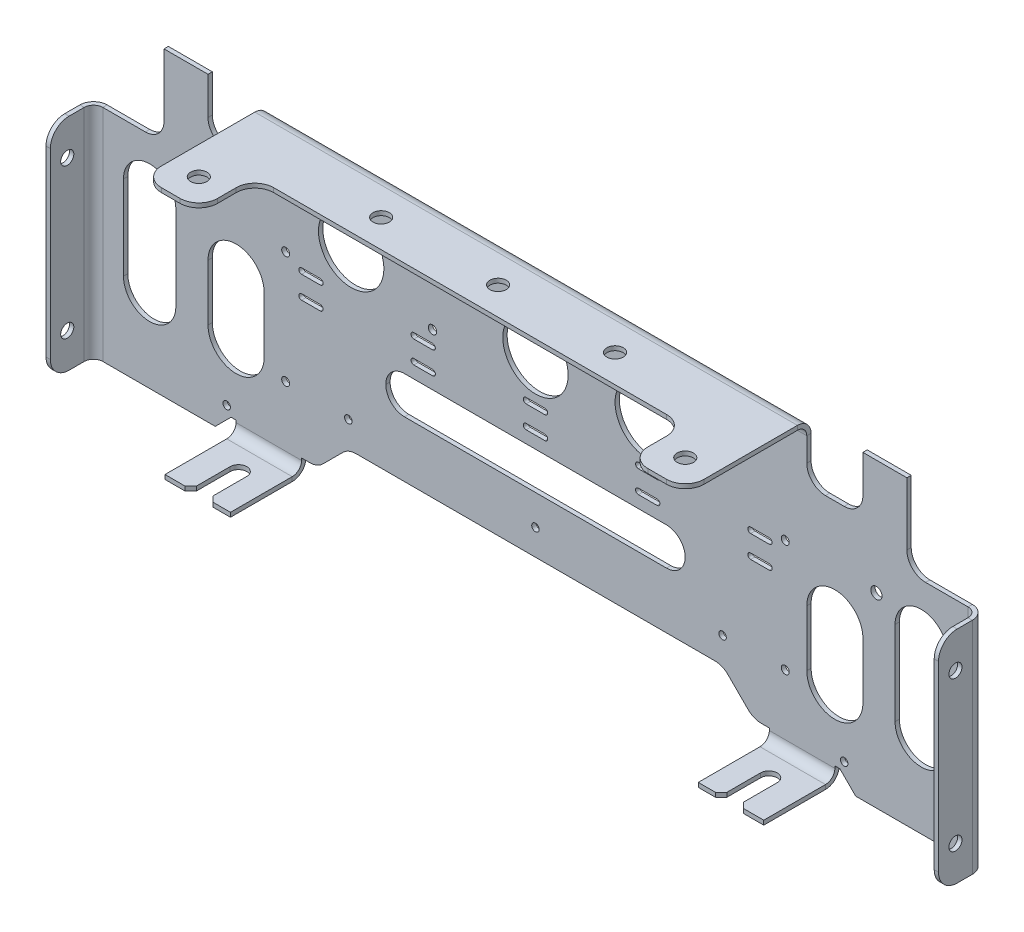
SolidWorks part; units mm, degrees
note: The reader was unsure of these and kept them because the rebuilt part matched: thickness of "Base-Flange1", "Edge-Flange1", "Edge-Flange2", "Edge-Flange3", "Sheet-Metal1", "Sheet-Metal2", "Sheet-Metal3", "Sheet-Metal4", "Sheet-Metal5", "Sheet-Metal6", "Sheet-Metal7", "Sheet-Metal14", "Sheet-Metal20", "Sheet-Metal21", "Sheet-Metal22", "Sheet-Metal24", "Sheet-Metal27", "Sheet-Metal28", "Sheet-Metal29", "Sheet-Metal30", "Sheet-Metal31", "Sheet-Metal32", "Sheet-Metal33"; flange length of "Edge-Flange1", "Edge-Flange2", "Edge-Flange3".
material "5052-H32"
ref_plane "Front Plane" through (0, 0, 0) normal (0, 0, 1) x (1, 0, 0)
ref_plane "Top Plane" through (0, 0, 0) normal (0, 1, 0) x (1, 0, 0)
ref_plane "Right Plane" through (0, 0, 0) normal (1, 0, 0) x (0, 0, -1)
sketch "Sketch1" plane through (0, 0, 0) normal (0, 0, 1) x (1, 0, 0)
  line L1 (238.5, 63.81) -> (-238.5, 63.81)
  line L2 (238.5, 63.81) -> (238.5, -63.81)
  line L3 (238.5, -63.81) -> (-238.5, -63.81)
  line L4 (-238.5, 63.81) -> (-238.5, -63.81)
  line L5 (238.5, 63.81) -> (-238.5, -63.81) construction
  line L6 (238.5, -63.81) -> (-238.5, 63.81) construction
  point P0 (0, 0)
  dimension "D1" = 477
  dimension "D2" = 127.62
base flange "Base-Flange1" sketch "Sketch1" thickness 2.31 reverse thickness direction no parameters "D1"=5
edge flange "Edge-Flange1" sketch "Sketch10" flange profiles "Sketch10", "Sketch11" flange angle 90 flange length 25.4 flange position material inside bend radius 5 thickness 2.31 parameters "D6"=10, "D8"=5.08
sketch "Sketch10" plane through (-238.5, 0, 0) normal (-1, 0, 0) x (0, -1, 0)
  line L2 (-63.81, 0) -> (-63.81, 23.09)
  line L3 (-63.81, 23.09) -> (63.81, 23.09)
  line L4 (63.81, 23.09) -> (63.81, 0)
  line L5 (-63.81, 0) -> (63.81, 0) construction
  line L6 (-63.81, 0) -> (63.81, 0)
sketch "Sketch11" plane through (238.5, 0, 0) normal (1, 0, 0) x (0, 1, 0)
  line L0 (-63.81, 0) -> (63.81, 0) construction
  line L1 (-63.81, 0) -> (63.81, 0)
  line L2 (-63.81, 0) -> (-63.81, 23.09)
  line L3 (-63.81, 23.09) -> (63.81, 23.09)
  line L4 (63.81, 23.09) -> (63.81, 0)
bend "EdgeBend1" bend radius 5 bend angle 90 parameters "D5"=1
bend "EdgeBend2" bend radius 5 bend angle 90 parameters "D5"=2
sketch "Sketch12" plane through (0, 0, 23.09) normal (0, 0, 1) x (1, 0, 0)
  line L0 (0, 63.81) -> (0, -63.81) construction
  line L1 (-238.5, 63.81) -> (-198.5, 63.81)
  line L2 (-238.5, 63.81) -> (-238.5, 53.81)
  line L3 (-238.5, 53.81) -> (-198.5, 53.81)
  line L4 (-198.5, 63.81) -> (-198.5, 53.81)
  line L5 (231.19, 63.81) -> (-231.19, 63.81) construction
  line L6 (-231.19, -63.81) -> (231.19, -63.81) construction
  line L7 (198.5, 63.81) -> (198.5, 53.81)
  line L8 (238.5, 53.81) -> (198.5, 53.81)
  line L9 (238.5, 63.81) -> (238.5, 53.81)
  line L10 (238.5, 63.81) -> (198.5, 63.81)
  dimension "D1" = 10
  dimension "D2" = 40
extrude "Cut-Extrude1" cut sketch "Sketch12" against normal through all
sketch "Sketch14" plane through (0, 0, 0) normal (0, 0, 1) x (1, 0, 0)
  line L0 (-231.19, -63.81) -> (231.19, -63.81) construction
  line L1 (198.5, 63.81) -> (-198.5, 63.81)
  line L2 (198.5, 63.81) -> (198.5, 97.24)
  line L3 (198.5, 97.24) -> (-198.5, 97.24)
  line L4 (-198.5, 63.81) -> (-198.5, 97.24)
  dimension "D1" = 161.05
extrude "Boss-Extrude1" add sketch "Sketch14" against normal up to surface (2.31 mm away) up to face at (0, 26.905, -2.31)
fillet "Fillet1" radius 10 4 edges at (-198.5, 53.81, -1.155) (198.5, 53.81, -1.155) (-237.345, 53.81, 23.09) (237.345, 53.81, 23.09)
sketch "Sketch15" plane through (238.5, 0, 0) normal (1, 0, 0) x (0, 0, -1)
  line L0 (-14.045, 35) -> (-14.045, -45) construction
  line L1 (-23.09, 43.81) -> (-23.09, -63.81) construction
  line L2 (-5, 53.81) -> (-5, -63.81) construction
  circle A0 centre (-14.045, 35) radius 3.5
  circle A1 centre (-14.045, -45) radius 3.5
  point P4 (-5, -5)
  point P6 (-14.045, -5)
  dimension "D1" = 7
  dimension "D2" = 80
  dimension "D3" = 9.045
extrude "Cut-Extrude3" cut sketch "Sketch15" against normal through all
sketch "Sketch16" plane through (0, 0, 0) normal (0, 0, 1) x (1, 0, 0)
  line L0 (125, -63.81) -> (100, -38.81)
  line L1 (-231.19, -63.81) -> (231.19, -63.81) construction
  line L2 (100, -38.81) -> (-100, -38.81)
  line L3 (-100, -38.81) -> (-125, -63.81)
  line L4 (-125, -63.81) -> (125, -63.81)
  point P4 (0, -63.81)
  dimension "D1" = 45
  dimension "D2" = 250
  dimension "D3" = 25
extrude "Cut-Extrude4" cut sketch "Sketch16" against normal blind 10
sketch "Sketch17" plane through (0, 0, 0) normal (0, 0, 1) x (1, 0, 0)
  line L0 (-160, 11.19) -> (-160, -18.81) construction
  line L1 (-145, 11.19) -> (-145, -18.81)
  line L2 (-175, 11.19) -> (-175, -18.81)
  line L3 (0, -38.81) -> (0, 97.24) construction
  line L4 (-100, -38.81) -> (100, -38.81) construction
  line L5 (198.5, 97.24) -> (-198.5, 97.24) construction
  line L6 (-231.19, -63.81) -> (-125, -63.81) construction
  line L7 (160, 11.19) -> (160, -18.81) construction
  line L8 (145, 11.19) -> (145, -18.81)
  line L9 (175, 11.19) -> (175, -18.81)
  line L10 (-206.19, 26.19) -> (-206.19, -18.81) construction
  line L11 (-192.19, 26.19) -> (-192.19, -18.81)
  line L12 (-220.19, 26.19) -> (-220.19, -18.81)
  line L13 (-231.19, -63.81) -> (-231.19, 53.81) construction
  line L14 (206.19, 26.19) -> (206.19, -18.81) construction
  line L15 (192.19, 26.19) -> (192.19, -18.81)
  line L16 (220.19, 26.19) -> (220.19, -18.81)
  line L17 (198.5, 97.24) -> (-198.5, 97.24) construction
  line L18 (175, 97.24) -> (145, 97.24)
  line L19 (175, 97.24) -> (175, 67.24)
  line L20 (175, 67.24) -> (145, 67.24)
  line L21 (145, 97.24) -> (145, 67.24)
  line L22 (-145, 97.24) -> (-145, 67.24)
  line L23 (-175, 67.24) -> (-145, 67.24)
  line L24 (-175, 97.24) -> (-175, 67.24)
  line L25 (-175, 97.24) -> (-145, 97.24)
  arc A0 (-145, 11.19) -> (-175, 11.19) centre (-160, 11.19) ccw
  arc A1 (-175, -18.81) -> (-145, -18.81) centre (-160, -18.81) ccw
  arc A2 (145, 11.19) -> (175, 11.19) centre (160, 11.19) cw
  arc A3 (175, -18.81) -> (145, -18.81) centre (160, -18.81) cw
  arc A4 (-192.19, 26.19) -> (-220.19, 26.19) centre (-206.19, 26.19) ccw
  arc A5 (-220.19, -18.81) -> (-192.19, -18.81) centre (-206.19, -18.81) ccw
  arc A6 (192.19, 26.19) -> (220.19, 26.19) centre (206.19, 26.19) cw
  arc A7 (220.19, -18.81) -> (192.19, -18.81) centre (206.19, -18.81) cw
  point P2 (-160, -3.81)
  point P18 (160, -3.81)
  point P25 (-206.19, 3.69)
  point P34 (206.19, 3.69)
  dimension "D2" = 15
  dimension "D5" = 14
  dimension "D1" = 30
  dimension "D3" = 60
  dimension "D4" = 160
  dimension "D6" = 25
  dimension "D7" = 45
  dimension "D8" = 30
extrude "Cut-Extrude5" cut sketch "Sketch17" against normal blind 10
sketch "Sketch18" plane through (0, 0, -2.31) normal (0, 0, -1) x (-1, 0, 0)
  line L0 (100, -38.81) -> (-100, -38.81) construction
  line L1 (80, 11.19) -> (-80, 11.19)
  line L2 (80, 11.19) -> (80, -8.81)
  line L3 (80, -8.81) -> (-80, -8.81)
  line L4 (-80, 11.19) -> (-80, -8.81)
  line L5 (80, 11.19) -> (-80, -8.81) construction
  line L6 (80, -8.81) -> (-80, 11.19) construction
  point P0 (0, 1.19)
  dimension "D1" = 20
  dimension "D2" = 160
  dimension "D3" = 30
extrude "Cut-Extrude6" cut sketch "Sketch18" against normal blind 10
sketch "Sketch19" plane through (0, 0, -2.31) normal (0, 0, -1) x (-1, 0, 0)
  line L0 (165, -50.955) -> (-165, -50.955) construction
  line L1 (-165, -50.955) -> (-100, -25) construction
  line L2 (-100, -25) -> (0, -25) construction
  line L3 (0, -25) -> (100, -25) construction
  line L4 (100, -25) -> (165, -50.955) construction
  circle A0 centre (0, -25) radius 2
  circle A1 centre (100, -25) radius 2
  circle A2 centre (165, -50.955) radius 2
  circle A3 centre (-100, -25) radius 2
  circle A4 centre (-165, -50.955) radius 2
  dimension "D1" = 4
  dimension "D2" = 330
  dimension "D3" = 25.955
  dimension "D4" = 65
  dimension "D5" = 25
extrude "Cut-Extrude8" cut sketch "Sketch19" against normal up to surface (2.31 mm away)
sketch "Sketch20" plane through (0, 0, -2.31) normal (0, 0, -1) x (-1, 0, 0)
  line L0 (60, 54.215) -> (-60, 54.215) construction
  line L1 (0, 11.19) -> (0, 97.24) construction
  line L2 (198.5, 63.81) -> (198.5, 97.24) construction
  line L3 (80, 11.19) -> (-80, 11.19) construction
  line L4 (-145, 97.24) -> (145, 97.24) construction
  circle A0 centre (0, 54.215) radius 17.4625
  circle A1 centre (98.5, 54.215) radius 17.4625
  circle A2 centre (-60, 54.215) radius 17.4625
  dimension "D1" = 34.925
  dimension "D2" = 120
  dimension "D3" = 100
extrude "Cut-Extrude9" cut sketch "Sketch20" against normal blind 10
fillet "Fillet2" radius 10 12 edges at (-80, -8.81, -1.155) (80, -8.81, -1.155) (80, 11.19, -1.155) (-80, 11.19, -1.155) (-100, -38.81, -1.155) (100, -38.81, -1.155) (-175, 67.24, -1.155) (-145, 67.24, -1.155) (175, 67.24, -1.155) (145, 67.24, -1.155) (237.345, -63.81, 23.09) (-237.345, -63.81, 23.09)
edge flange "Edge-Flange2" sketch "Sketch28" flange angle 90 flange length 34.925 flange position material inside bend radius 5 thickness 2.31 parameters "D1"=9.525, "D6"=10
bend "EdgeBend4" bend radius 5 bend angle 90 parameters "D5"=3
sketch "Sketch28" plane through (0, 97.24, 0) normal (0, 1, 0) x (-1, 0, 0)
  line L1 (-145, 0) -> (145, 0) construction
  line L2 (145, 0) -> (145, 34.925)
  line L3 (145, 34.925) -> (-145, 34.925)
  line L4 (-145, 34.925) -> (-145, 0)
  line L5 (-145, 0) -> (145, 0)
sketch "Sketch30" plane through (0, 0, -2.31) normal (0, 0, -1) x (-1, 0, 0)
  circle A0 centre (55.008, 69.045) radius 2.25
  circle A1 centre (55.008, 39.045) radius 2.25
  dimension "D1" = 4.5
extrude "Cut-Extrude11" cut sketch "Sketch30" against normal blind 10
sketch "Sketch32" plane through (0, 97.24, 0) normal (0, 1, 0) x (1, 0, 0)
  line L0 (0, 0) -> (0, -34.925) construction
  line L1 (-145, -34.925) -> (-115, -34.925)
  line L2 (-145, -34.925) -> (-145, -64.925)
  line L3 (-145, -64.925) -> (-115, -64.925)
  line L4 (-115, -34.925) -> (-115, -64.925)
  line L5 (-145, -34.925) -> (145, -34.925) construction
  line L6 (115, -34.925) -> (115, -64.925)
  line L7 (145, -64.925) -> (115, -64.925)
  line L8 (145, -34.925) -> (145, -64.925)
  line L9 (145, -34.925) -> (115, -34.925)
  dimension "D1" = 30
extrude "Boss-Extrude2" add sketch "Sketch32" against normal up to surface (2.31 mm away) up to face at (0, 94.93, 19.9625)
fillet "Fillet3" radius 10 6 edges at (115, 96.085, 34.925) (145, 96.085, 64.925) (115, 96.085, 64.925) (-145, 96.085, 64.925) (-115, 96.085, 64.925)
sketch "Sketch29" plane through (0, 97.24, 0) normal (0, 1, 0) x (1, 0, 0)
  line L0 (0, -19.9625) -> (125, -19.9625) construction
  line L1 (145, -54.925) -> (145, -5) construction
  line L2 (0, -34.925) -> (0, -5) construction
  line L3 (-105, -34.925) -> (105, -34.925) construction
  line L4 (145, -5) -> (-145, -5) construction
  line L6 (125, -64.925) -> (135, -64.925) construction
  line L7 (115, -44.925) -> (115, -54.925) construction
  line L8 (-135, -64.925) -> (-125, -64.925) construction
  circle A0 centre (0, -19.9625) radius 4.375
  circle A1 centre (62.5, -19.9625) radius 4.375
  circle A2 centre (-130, -49.925) radius 4.375
  circle A3 centre (130, -49.925) radius 4.375
  circle A4 centre (-62.5, -19.9625) radius 4.375
  point P20 (130, -64.925)
  point P21 (115, -49.925)
  point P24 (-130, -64.925)
  dimension "D1" = 8.75
  dimension "D3" = 8.75
  dimension "D2" = 20
extrude "Cut-Extrude10" cut sketch "Sketch29" against normal blind 10
sketch "Sketch33" plane through (0, 0, -2.31) normal (0, 0, -1) x (-1, 0, 0)
  line L0 (-115, 19.19) -> (-125, 19.19) construction
  line L1 (-115, 17.69) -> (-125, 17.69)
  line L2 (-115, 20.69) -> (-125, 20.69)
  line L3 (-115, 31.19) -> (-125, 31.19) construction
  line L4 (-115, 29.69) -> (-125, 29.69)
  line L5 (-115, 32.69) -> (-125, 32.69)
  line L6 (70, 11.19) -> (-70, 11.19) construction
  line L7 (-55, 19.19) -> (-65, 19.19) construction
  line L8 (-55, 17.69) -> (-65, 17.69)
  line L9 (-55, 20.69) -> (-65, 20.69)
  line L10 (-55, 31.19) -> (-65, 31.19) construction
  line L11 (-55, 29.69) -> (-65, 29.69)
  line L12 (-55, 32.69) -> (-65, 32.69)
  line L13 (-115, 31.19) -> (-55, 31.19) construction
  line L14 (5, 19.19) -> (-5, 19.19) construction
  line L15 (5, 17.69) -> (-5, 17.69)
  line L16 (5, 20.69) -> (-5, 20.69)
  line L17 (5, 31.19) -> (-5, 31.19) construction
  line L18 (5, 29.69) -> (-5, 29.69)
  line L19 (5, 32.69) -> (-5, 32.69)
  line L20 (65, 19.19) -> (55, 19.19) construction
  line L21 (65, 17.69) -> (55, 17.69)
  line L22 (65, 20.69) -> (55, 20.69)
  line L23 (65, 31.19) -> (55, 31.19) construction
  line L24 (65, 29.69) -> (55, 29.69)
  line L25 (65, 32.69) -> (55, 32.69)
  line L26 (125, 19.19) -> (115, 19.19) construction
  line L27 (125, 17.69) -> (115, 17.69)
  line L28 (125, 20.69) -> (115, 20.69)
  line L29 (125, 31.19) -> (115, 31.19) construction
  line L30 (125, 29.69) -> (115, 29.69)
  line L31 (125, 32.69) -> (115, 32.69)
  arc A0 (-115, 17.69) -> (-115, 20.69) centre (-115, 19.19) ccw
  arc A1 (-125, 20.69) -> (-125, 17.69) centre (-125, 19.19) ccw
  arc A2 (-115, 29.69) -> (-115, 32.69) centre (-115, 31.19) ccw
  arc A3 (-125, 32.69) -> (-125, 29.69) centre (-125, 31.19) ccw
  arc A4 (-55, 17.69) -> (-55, 20.69) centre (-55, 19.19) ccw
  arc A5 (-65, 20.69) -> (-65, 17.69) centre (-65, 19.19) ccw
  arc A6 (-55, 29.69) -> (-55, 32.69) centre (-55, 31.19) ccw
  arc A7 (-65, 32.69) -> (-65, 29.69) centre (-65, 31.19) ccw
  arc A8 (5, 17.69) -> (5, 20.69) centre (5, 19.19) ccw
  arc A9 (-5, 20.69) -> (-5, 17.69) centre (-5, 19.19) ccw
  arc A10 (5, 29.69) -> (5, 32.69) centre (5, 31.19) ccw
  arc A11 (-5, 32.69) -> (-5, 29.69) centre (-5, 31.19) ccw
  arc A12 (65, 17.69) -> (65, 20.69) centre (65, 19.19) ccw
  arc A13 (55, 20.69) -> (55, 17.69) centre (55, 19.19) ccw
  arc A14 (65, 29.69) -> (65, 32.69) centre (65, 31.19) ccw
  arc A15 (55, 32.69) -> (55, 29.69) centre (55, 31.19) ccw
  arc A16 (125, 17.69) -> (125, 20.69) centre (125, 19.19) ccw
  arc A17 (115, 20.69) -> (115, 17.69) centre (115, 19.19) ccw
  arc A18 (125, 29.69) -> (125, 32.69) centre (125, 31.19) ccw
  arc A19 (115, 32.69) -> (115, 29.69) centre (115, 31.19) ccw
  point P2 (-120, 19.19)
  point P9 (-120, 31.19)
  point P20 (-60, 19.19)
  point P27 (-60, 31.19)
  point P35 (0, 19.19)
  point P42 (0, 31.19)
  point P49 (60, 19.19)
  point P56 (60, 31.19)
  point P63 (120, 19.19)
  point P70 (120, 31.19)
  dimension "D1" = 1.5
  dimension "D2" = 12
  dimension "D3" = 120
  dimension "D4" = 10
  dimension "D5" = 8
  dimension "D7" = 60
  dimension "D6" = 5
extrude "Cut-Extrude12" cut sketch "Sketch33" against normal blind 10
edge flange "Edge-Flange3" sketch "Sketch38" flange profiles "Sketch38", "Sketch39" flange angle 90 flange length 38 flange position material inside bend radius 5 thickness 2.31 parameters "D6"=10, "D8"=1
sketch "Sketch38" plane through (0, -63.81, 0) normal (0, -1, 0) x (1, 0, 0)
  line L0 (-231.19, 0) -> (-125, 0) construction
  line L1 (-160, 0) -> (-125, 0)
  line L2 (-160, 0) -> (-160, 38)
  line L3 (-160, 38) -> (-125, 38)
  line L4 (-125, 38) -> (-125, 0)
  dimension "D1" = 35
sketch "Sketch39" plane through (0, -63.81, 0) normal (0, -1, 0) x (1, 0, 0)
  line L0 (125, 0) -> (231.19, 0) construction
  line L1 (125, 0) -> (160, 0)
  line L2 (125, 0) -> (125, 38)
  line L3 (125, 38) -> (160, 38)
  line L4 (160, 38) -> (160, 0)
  line L5 (-160, 38) -> (-125, 38) construction
bend "EdgeBend5" bend radius 5 bend angle 90 parameters "D5"=4
bend "EdgeBend6" bend radius 5 bend angle 90 parameters "D5"=5
sketch "Sketch40" plane through (0, 0, 0) normal (0, 0, 1) x (1, 0, 0)
  line L0 (0, 0) -> (0, -38.81) construction
  line L1 (-123.845, -55.345) -> (-113.845, -55.345)
  line L2 (-123.845, -55.345) -> (-123.845, -62.655)
  line L3 (-123.845, -62.655) -> (-113.845, -62.655)
  line L4 (-113.845, -55.345) -> (-113.845, -62.655)
  line L5 (-95.8579, -38.81) -> (95.8579, -38.81) construction
  line L6 (113.845, -55.345) -> (113.845, -62.655)
  line L7 (123.845, -62.655) -> (113.845, -62.655)
  line L8 (123.845, -55.345) -> (123.845, -62.655)
  line L9 (123.845, -55.345) -> (113.845, -55.345)
  dimension "D1" = 10
extrude "Cut-Extrude13" cut sketch "Sketch40" against normal blind 10
fillet "Fillet4" radius 10 2 edges at (116.535, -55.345, -1.155) (-116.535, -55.345, -1.155)
chamfer "Chamfer1" distance 10 angle 45 8 edges at (-161.155, -59.5775, -2.31) (-161.155, -55.345, -1.155) (-161.155, -59.5775, 0) (-161.155, -63.81, -1.155) (161.155, -59.5775, -2.31) (161.155, -63.81, -1.155) (161.155, -59.5775, 0) (161.155, -55.345, -1.155)
sketch "Sketch41" plane through (0, -61.5, 0) normal (0, 1, 0) x (1, 0, 0)
  line L0 (146.243, -17) -> (146.243, -38)
  line L1 (160, -38) -> (125, -38) construction
  line L2 (146.243, -38) -> (137.243, -38)
  line L3 (137.243, -38) -> (137.243, -17)
  line L4 (0, -34.925) -> (0, -24.3375) construction
  line L5 (-105, -34.925) -> (105, -34.925) construction
  line L6 (-137.243, -38) -> (-137.243, -17)
  line L7 (-146.243, -38) -> (-137.243, -38)
  line L8 (-146.243, -17) -> (-146.243, -38)
  line L9 (125, -5) -> (160, -5) construction
  arc A0 (146.243, -17) -> (137.243, -17) centre (141.743, -17) ccw
  circle A1 centre (0, -19.9625) radius 4.375 construction
  arc A2 (-146.243, -17) -> (-137.243, -17) centre (-141.743, -17) cw
  point P1 (141.743, -32.9521)
  point P20 (-142.5, -38)
  dimension "D1" = 9
  dimension "D2" = 12
extrude "Cut-Extrude14" cut sketch "Sketch41" against normal blind 10
chamfer "Chamfer2" distance 3 angle 45 4 edges at (137.243, -62.655, 38) (146.243, -62.655, 38) (-137.243, -62.655, 38) (-146.243, -62.655, 38)
sketch "Sketch42" plane through (0, 0, 0) normal (0, 0, 1) x (1, 0, 0)
  line L0 (-208.5, 53.81) -> (-231.19, 53.81) construction
  line L1 (-238.5, -53.81) -> (-238.5, 43.81) construction
  line L2 (0, 0) -> (0, -8.81) construction
  line L3 (70, -8.81) -> (-70, -8.81) construction
  line L4 (-192.19, 26.19) -> (-192.19, -18.81) construction
  circle A0 centre (-133.5, 35.81) radius 2.125
  circle A1 centre (-133.5, -24.19) radius 2.125
  circle A2 centre (133.5, -24.19) radius 2.125
  circle A3 centre (133.5, 35.81) radius 2.125
  circle A4 centre (-182.19, 35.81) radius 3
  circle A5 centre (182.19, 35.81) radius 3
  dimension "D1" = 4.25
  dimension "D5" = 6
  dimension "D2" = 18
  dimension "D3" = 60
  dimension "D4" = 105
  dimension "D6" = 10
extrude "Cut-Extrude15" cut sketch "Sketch42" against normal blind 10
sketch "Bend-Lines1" [suppressed] plane through (0, 0, 0) normal (0, 1, 0) x (1, 0, 0)
sketch "Bounding-Box1" [suppressed] plane through (0, 0, 0) normal (0, 1, 0) x (1, 0, 0)
sheet metal parameters "Sheet-Metal1" thickness 2.31 parameters "D1"=9.525, "D7"=4.78
flat pattern "Flat-Pattern1" [suppressed]
sketch "Bend-Lines2" plane through (0, 0, 0) normal (0, 1, 0) x (1, 0, 0)
sketch "Bounding-Box2" [suppressed] plane through (0, 0, 0) normal (0, 1, 0) x (1, 0, 0)
sheet metal parameters "Sheet-Metal2" thickness 2.31 parameters "D1"=9.525, "D7"=4.78
flat pattern "Flat-Pattern1" [suppressed]
sketch "Bend-Lines2" plane through (0, 0, 0) normal (0, 1, 0) x (1, 0, 0)
sketch "Bounding-Box2" [suppressed] plane through (0, 0, 0) normal (0, 1, 0) x (1, 0, 0)
bend of the flat pattern "Flatten-<EdgeBend1>1"
bend of the flat pattern "Flatten-<EdgeBend2>1"
sheet metal parameters "Sheet-Metal3" thickness 2.31 parameters "D1"=9.525, "D7"=4.78
flat pattern "Flat-Pattern1" [suppressed]
sketch "Bend-Lines2" plane through (0, 0, 0) normal (0, 1, 0) x (1, 0, 0)
sketch "Bounding-Box2" [suppressed] plane through (0, 0, 0) normal (0, 1, 0) x (1, 0, 0)
bend of the flat pattern "Flatten-<EdgeBend1>1"
bend of the flat pattern "Flatten-<EdgeBend2>1"
sheet metal parameters "Sheet-Metal4" thickness 2.31 parameters "D1"=9.525, "D7"=4.78
flat pattern "Flat-Pattern1" [suppressed]
sketch "Bend-Lines2" plane through (0, 0, 0) normal (0, 1, 0) x (1, 0, 0)
sketch "Bounding-Box2" [suppressed] plane through (0, 0, 0) normal (0, 1, 0) x (1, 0, 0)
bend of the flat pattern "Flatten-<EdgeBend1>1"
bend of the flat pattern "Flatten-<EdgeBend2>1"
sheet metal parameters "Sheet-Metal5" thickness 2.31 parameters "D1"=9.525, "D7"=4.78
flat pattern "Flat-Pattern1" [suppressed]
sketch "Bend-Lines2" plane through (0, 0, 0) normal (0, 1, 0) x (1, 0, 0)
sketch "Bounding-Box2" [suppressed] plane through (0, 0, 0) normal (0, 1, 0) x (1, 0, 0)
bend of the flat pattern "Flatten-<EdgeBend1>1"
bend of the flat pattern "Flatten-<EdgeBend2>1"
sheet metal parameters "Sheet-Metal6" thickness 2.31 parameters "D1"=9.525, "D7"=4.78
flat pattern "Flat-Pattern1"
sketch "Bend-Lines2" plane through (0, 0, 0) normal (0, 0, 1) x (1, 0, 0)
  line L0 (233.553, -63.81) -> (233.553, 53.81) construction
  line L1 (-233.553, 53.81) -> (-233.553, -63.81) construction
  line L2 (233.553, -63.81) -> (233.553, 53.81) construction
  line L3 (-233.553, 53.81) -> (-233.553, -63.81) construction
sketch3d "Bounding-Box2" [suppressed]
  line L0 (-263.531, 93.81, 0) -> (263.531, 93.81, 0) construction
  line L1 (-263.531, -63.81, 0) -> (263.531, -63.81, 0) construction
  line L2 (-263.531, 93.81, 0) -> (-263.531, -63.81, 0) construction
  line L3 (263.531, 93.81, 0) -> (263.531, -63.81, 0) construction
bend of the flat pattern "Flatten-<EdgeBend1>1"
bend of the flat pattern "Flatten-<EdgeBend2>1"
sheet metal parameters "Sheet-Metal7" thickness 2.31 parameters "D1"=9.525, "D7"=4.78
flat pattern "Flat-Pattern1"
sketch "Bend-Lines2" plane through (0, 0, 0) normal (0, 0, 1) x (1, 0, 0)
  line L0 (233.553, -63.81) -> (233.553, 53.81) construction
  line L1 (-233.553, 53.81) -> (-233.553, -63.81) construction
  line L2 (233.553, -63.81) -> (233.553, 53.81) construction
  line L3 (-233.553, 53.81) -> (-233.553, -63.81) construction
sketch3d "Bounding-Box2" [suppressed]
  line L0 (-263.531, 93.81, 0) -> (263.531, 93.81, 0) construction
  line L1 (-263.531, -63.81, 0) -> (263.531, -63.81, 0) construction
  line L2 (-263.531, 93.81, 0) -> (-263.531, -63.81, 0) construction
  line L3 (263.531, 93.81, 0) -> (263.531, -63.81, 0) construction
bend of the flat pattern "Flatten-<EdgeBend1>1"
bend of the flat pattern "Flatten-<EdgeBend2>1"
sheet metal parameters "Sheet-Metal14" thickness 2.31 parameters "D1"=9.525, "D7"=4.78
flat pattern "Flat-Pattern1"
sketch "Bend-Lines2" plane through (0, 0, 0) normal (0, 0, 1) x (1, 0, 0)
  line L0 (233.553, -63.81) -> (233.553, 53.81) construction
  line L1 (-233.553, 53.81) -> (-233.553, -63.81) construction
  line L2 (233.553, -63.81) -> (233.553, 53.81) construction
  line L3 (-233.553, 53.81) -> (-233.553, -63.81) construction
sketch3d "Bounding-Box2" [suppressed]
  line L0 (-263.531, 93.81, 0) -> (263.531, 93.81, 0) construction
  line L1 (-263.531, -63.81, 0) -> (263.531, -63.81, 0) construction
  line L2 (-263.531, 93.81, 0) -> (-263.531, -63.81, 0) construction
  line L3 (263.531, 93.81, 0) -> (263.531, -63.81, 0) construction
bend of the flat pattern "Flatten-<EdgeBend1>1"
bend of the flat pattern "Flatten-<EdgeBend2>1"
sheet metal parameters "Sheet-Metal20" thickness 2.31 parameters "D1"=9.525, "D7"=4.78
flat pattern "Flat-Pattern1"
sketch "Bend-Lines2" plane through (0, 0, 0) normal (0, 0, 1) x (1, 0, 0)
  line L0 (233.553, -63.81) -> (233.553, 53.81) construction
  line L1 (-233.553, 53.81) -> (-233.553, -63.81) construction
  line L2 (233.553, -63.81) -> (233.553, 53.81) construction
  line L3 (-233.553, 53.81) -> (-233.553, -63.81) construction
sketch3d "Bounding-Box2" [suppressed]
  line L0 (-263.531, 93.81, 0) -> (263.531, 93.81, 0) construction
  line L1 (-263.531, -63.81, 0) -> (263.531, -63.81, 0) construction
  line L2 (-263.531, 93.81, 0) -> (-263.531, -63.81, 0) construction
  line L3 (263.531, 93.81, 0) -> (263.531, -63.81, 0) construction
bend of the flat pattern "Flatten-<EdgeBend1>1"
bend of the flat pattern "Flatten-<EdgeBend2>1"
sheet metal parameters "Sheet-Metal21" thickness 2.31 parameters "D1"=9.525, "D7"=4.78
flat pattern "Flat-Pattern1"
sketch "Bend-Lines2" plane through (0, 0, 0) normal (0, 0, 1) x (1, 0, 0)
  line L0 (233.553, -63.81) -> (233.553, 53.81) construction
  line L1 (-233.553, 53.81) -> (-233.553, -63.81) construction
  line L2 (233.553, -63.81) -> (233.553, 53.81) construction
  line L3 (-233.553, 53.81) -> (-233.553, -63.81) construction
sketch3d "Bounding-Box2" [suppressed]
  line L0 (-263.531, 93.81, 0) -> (263.531, 93.81, 0) construction
  line L1 (-263.531, -63.81, 0) -> (263.531, -63.81, 0) construction
  line L2 (-263.531, 93.81, 0) -> (-263.531, -63.81, 0) construction
  line L3 (263.531, 93.81, 0) -> (263.531, -63.81, 0) construction
bend of the flat pattern "Flatten-<EdgeBend1>1"
bend of the flat pattern "Flatten-<EdgeBend2>1"
sheet metal parameters "Sheet-Metal22" thickness 2.31 parameters "D1"=9.525, "D7"=4.78
flat pattern "Flat-Pattern1" [suppressed]
sketch "Bend-Lines2" plane through (0, 0, 0) normal (0, 0, 1) x (1, 0, 0)
  line L0 (233.553, -63.81) -> (233.553, 53.81) construction
  line L1 (-233.553, 53.81) -> (-233.553, -63.81) construction
  line L2 (233.553, -63.81) -> (233.553, 53.81) construction
  line L3 (-233.553, 53.81) -> (-233.553, -63.81) construction
sketch3d "Bounding-Box2" [suppressed]
  line L0 (-263.531, 93.81, 0) -> (263.531, 93.81, 0) construction
  line L1 (-263.531, -63.81, 0) -> (263.531, -63.81, 0) construction
  line L2 (-263.531, 93.81, 0) -> (-263.531, -63.81, 0) construction
  line L3 (263.531, 93.81, 0) -> (263.531, -63.81, 0) construction
bend of the flat pattern "Flatten-<EdgeBend1>1"
bend of the flat pattern "Flatten-<EdgeBend2>1"
bend of the flat pattern "Flatten-<EdgeBend4>1"
sheet metal parameters "Sheet-Metal24" thickness 2.31 parameters "D1"=9.525, "D7"=4.78
flat pattern "Flat-Pattern1" [suppressed]
sketch "Bend-Lines2" plane through (0, 0, 0) normal (0, 0, 1) x (1, 0, 0)
  line L0 (233.553, -63.81) -> (233.553, 53.81) construction
  line L1 (-233.553, 53.81) -> (-233.553, -63.81) construction
  line L2 (233.553, -63.81) -> (233.553, 53.81) construction
  line L3 (-233.553, 53.81) -> (-233.553, -63.81) construction
sketch3d "Bounding-Box2" [suppressed]
  line L0 (-263.531, 93.81, 0) -> (263.531, 93.81, 0) construction
  line L1 (-263.531, -63.81, 0) -> (263.531, -63.81, 0) construction
  line L2 (-263.531, 93.81, 0) -> (-263.531, -63.81, 0) construction
  line L3 (263.531, 93.81, 0) -> (263.531, -63.81, 0) construction
bend of the flat pattern "Flatten-<EdgeBend1>1"
bend of the flat pattern "Flatten-<EdgeBend2>1"
bend of the flat pattern "Flatten-<EdgeBend4>1"
sheet metal parameters "Sheet-Metal27" thickness 2.31 parameters "D1"=9.525, "D7"=4.78
flat pattern "Flat-Pattern1" [suppressed]
sketch "Bend-Lines2" plane through (0, 0, 0) normal (0, 0, 1) x (1, 0, 0)
  line L0 (233.553, -63.81) -> (233.553, 53.81) construction
  line L1 (-233.553, 53.81) -> (-233.553, -63.81) construction
  line L2 (233.553, -63.81) -> (233.553, 53.81) construction
  line L3 (-233.553, 53.81) -> (-233.553, -63.81) construction
sketch3d "Bounding-Box2" [suppressed]
  line L0 (-263.531, 93.81, 0) -> (263.531, 93.81, 0) construction
  line L1 (-263.531, -63.81, 0) -> (263.531, -63.81, 0) construction
  line L2 (-263.531, 93.81, 0) -> (-263.531, -63.81, 0) construction
  line L3 (263.531, 93.81, 0) -> (263.531, -63.81, 0) construction
bend of the flat pattern "Flatten-<EdgeBend1>1"
bend of the flat pattern "Flatten-<EdgeBend2>1"
bend of the flat pattern "Flatten-<EdgeBend4>1"
sheet metal parameters "Sheet-Metal28" thickness 2.31 parameters "D1"=9.525, "D7"=4.78
flat pattern "Flat-Pattern1" [suppressed]
sketch "Bend-Lines2" plane through (0, 0, 0) normal (0, 0, 1) x (1, 0, 0)
  line L0 (233.553, -63.81) -> (233.553, 53.81) construction
  line L1 (-233.553, 53.81) -> (-233.553, -63.81) construction
  line L2 (233.553, -63.81) -> (233.553, 53.81) construction
  line L3 (-233.553, 53.81) -> (-233.553, -63.81) construction
sketch3d "Bounding-Box2" [suppressed]
  line L0 (-263.531, 93.81, 0) -> (263.531, 93.81, 0) construction
  line L1 (-263.531, -63.81, 0) -> (263.531, -63.81, 0) construction
  line L2 (-263.531, 93.81, 0) -> (-263.531, -63.81, 0) construction
  line L3 (263.531, 93.81, 0) -> (263.531, -63.81, 0) construction
bend of the flat pattern "Flatten-<EdgeBend1>1"
bend of the flat pattern "Flatten-<EdgeBend2>1"
bend of the flat pattern "Flatten-<EdgeBend4>1"
sheet metal parameters "Sheet-Metal29" thickness 2.31 parameters "D1"=9.525, "D7"=4.78
flat pattern "Flat-Pattern1" [suppressed]
sketch "Bend-Lines2" plane through (0, 0, 0) normal (0, 0, 1) x (1, 0, 0)
  line L0 (233.553, -63.81) -> (233.553, 53.81) construction
  line L1 (-233.553, 53.81) -> (-233.553, -63.81) construction
  line L2 (233.553, -63.81) -> (233.553, 53.81) construction
  line L3 (-233.553, 53.81) -> (-233.553, -63.81) construction
sketch3d "Bounding-Box2" [suppressed]
  line L0 (-263.531, 93.81, 0) -> (263.531, 93.81, 0) construction
  line L1 (-263.531, -63.81, 0) -> (263.531, -63.81, 0) construction
  line L2 (-263.531, 93.81, 0) -> (-263.531, -63.81, 0) construction
  line L3 (263.531, 93.81, 0) -> (263.531, -63.81, 0) construction
bend of the flat pattern "Flatten-<EdgeBend1>1"
bend of the flat pattern "Flatten-<EdgeBend2>1"
bend of the flat pattern "Flatten-<EdgeBend4>1"
sheet metal parameters "Sheet-Metal30" thickness 2.31 parameters "D1"=9.525, "D7"=4.78
flat pattern "Flat-Pattern1" [suppressed]
sketch "Bend-Lines2" plane through (0, 0, 0) normal (0, 0, 1) x (1, 0, 0)
  line L0 (233.553, -63.81) -> (233.553, 53.81) construction
  line L1 (-233.553, 53.81) -> (-233.553, -63.81) construction
  line L2 (233.553, -63.81) -> (233.553, 53.81) construction
  line L3 (-233.553, 53.81) -> (-233.553, -63.81) construction
sketch3d "Bounding-Box2" [suppressed]
  line L0 (-263.531, 93.81, 0) -> (263.531, 93.81, 0) construction
  line L1 (-263.531, -63.81, 0) -> (263.531, -63.81, 0) construction
  line L2 (-263.531, 93.81, 0) -> (-263.531, -63.81, 0) construction
  line L3 (263.531, 93.81, 0) -> (263.531, -63.81, 0) construction
bend of the flat pattern "Flatten-<EdgeBend1>1"
bend of the flat pattern "Flatten-<EdgeBend2>1"
bend of the flat pattern "Flatten-<EdgeBend4>1"
bend of the flat pattern "Flatten-<EdgeBend5>1"
bend of the flat pattern "Flatten-<EdgeBend6>1"
sheet metal parameters "Sheet-Metal31" thickness 2.31 parameters "D1"=9.525, "D7"=4.78
flat pattern "Flat-Pattern1"
sketch "Bend-Lines2" plane through (0, 0, 0) normal (0, 0, 1) x (1, 0, 0)
  line L0 (234.5241, -63.81) -> (234.5241, 53.81) construction
  line L1 (-234.5241, 53.81) -> (-234.5241, -63.81) construction
  line L2 (234.5241, -63.81) -> (234.5241, 53.81) construction
  line L3 (-234.5241, 53.81) -> (-234.5241, -63.81) construction
  line L4 (125, -59.8341) -> (155, -59.8341) construction
  line L5 (-155, -59.8341) -> (-125, -59.8341) construction
  line L6 (145, 97.7141) -> (-145, 97.7141) construction
  line L7 (125, -59.8341) -> (155, -59.8341) construction
  line L8 (-155, -59.8341) -> (-125, -59.8341) construction
  line L9 (145, 97.7141) -> (-145, 97.7141) construction
sketch3d "Bounding-Box2" [suppressed]
  line L0 (-255.9482, 163.4432, 0) -> (255.9482, 163.4432, 0) construction
  line L1 (-255.9482, -95.5632, 0) -> (255.9482, -95.5632, 0) construction
  line L2 (-255.9482, 163.4432, 0) -> (-255.9482, -95.5632, 0) construction
  line L3 (255.9482, 163.4432, 0) -> (255.9482, -95.5632, 0) construction
bend of the flat pattern "Flatten-<EdgeBend1>1"
bend of the flat pattern "Flatten-<EdgeBend2>1"
bend of the flat pattern "Flatten-<EdgeBend4>1"
bend of the flat pattern "Flatten-<EdgeBend5>1"
bend of the flat pattern "Flatten-<EdgeBend6>1"
sheet metal parameters "Sheet-Metal32" thickness 2.31 parameters "D1"=9.525, "D7"=4.78
flat pattern "Flat-Pattern1"
sketch "Bend-Lines2" plane through (0, 0, 0) normal (0, 0, 1) x (1, 0, 0)
  line L0 (234.5241, -63.81) -> (234.5241, 53.81) construction
  line L1 (-234.5241, 53.81) -> (-234.5241, -63.81) construction
  line L2 (234.5241, -63.81) -> (234.5241, 53.81) construction
  line L3 (-234.5241, 53.81) -> (-234.5241, -63.81) construction
  line L4 (125, -59.8341) -> (155, -59.8341) construction
  line L5 (-155, -59.8341) -> (-125, -59.8341) construction
  line L6 (145, 97.7141) -> (-145, 97.7141) construction
  line L7 (125, -59.8341) -> (155, -59.8341) construction
  line L8 (-155, -59.8341) -> (-125, -59.8341) construction
  line L9 (145, 97.7141) -> (-145, 97.7141) construction
sketch3d "Bounding-Box2" [suppressed]
  line L0 (-255.9482, 163.4432, 0) -> (255.9482, 163.4432, 0) construction
  line L1 (-255.9482, -95.5632, 0) -> (255.9482, -95.5632, 0) construction
  line L2 (-255.9482, 163.4432, 0) -> (-255.9482, -95.5632, 0) construction
  line L3 (255.9482, 163.4432, 0) -> (255.9482, -95.5632, 0) construction
bend of the flat pattern "Flatten-<EdgeBend1>1"
bend of the flat pattern "Flatten-<EdgeBend2>1"
bend of the flat pattern "Flatten-<EdgeBend4>1"
bend of the flat pattern "Flatten-<EdgeBend5>1"
bend of the flat pattern "Flatten-<EdgeBend6>1"
sheet metal parameters "Sheet-Metal33" thickness 2.31 parameters "D1"=9.525, "D7"=4.78
flat pattern "Flat-Pattern1"
sketch "Bend-Lines2" plane through (0, 0, 0) normal (0, 0, 1) x (1, 0, 0)
  line L0 (234.5241, -63.81) -> (234.5241, 53.81) construction
  line L1 (-234.5241, 53.81) -> (-234.5241, -63.81) construction
  line L2 (234.5241, -63.81) -> (234.5241, 53.81) construction
  line L3 (-234.5241, 53.81) -> (-234.5241, -63.81) construction
  line L4 (125, -59.8341) -> (155, -59.8341) construction
  line L5 (-155, -59.8341) -> (-125, -59.8341) construction
  line L6 (145, 97.7141) -> (-145, 97.7141) construction
  line L7 (125, -59.8341) -> (155, -59.8341) construction
  line L8 (-155, -59.8341) -> (-125, -59.8341) construction
  line L9 (145, 97.7141) -> (-145, 97.7141) construction
sketch3d "Bounding-Box2" [suppressed]
  line L0 (-255.9482, 163.4432, 0) -> (255.9482, 163.4432, 0) construction
  line L1 (-255.9482, -98.6382, 0) -> (255.9482, -98.6382, 0) construction
  line L2 (-255.9482, 163.4432, 0) -> (-255.9482, -98.6382, 0) construction
  line L3 (255.9482, 163.4432, 0) -> (255.9482, -98.6382, 0) construction
bend of the flat pattern "Flatten-<EdgeBend1>1"
bend of the flat pattern "Flatten-<EdgeBend2>1"
bend of the flat pattern "Flatten-<EdgeBend4>1"
bend of the flat pattern "Flatten-<EdgeBend5>1"
bend of the flat pattern "Flatten-<EdgeBend6>1"
